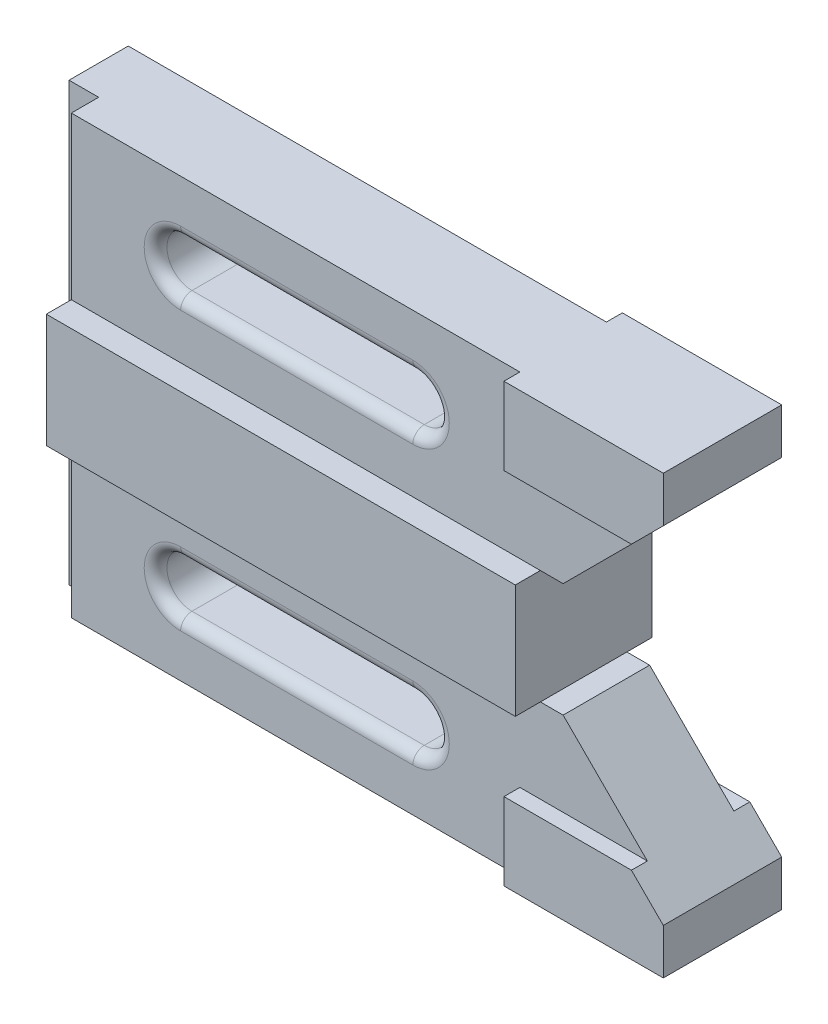
SolidWorks part; units mm, degrees
material "1060 Alloy"
ref_plane "Front Plane" through (0, 0, 0) normal (0, 0, 1) x (1, 0, 0)
ref_plane "Top Plane" through (0, 0, 0) normal (0, 1, 0) x (1, 0, 0)
ref_plane "Right Plane" through (0, 0, 0) normal (1, 0, 0) x (0, 0, -1)
sketch "Sketch2" plane through (0, 0, 0) normal (0, 0, 1) x (1, 0, 0)
  line L0 (0, 0) -> (0, 48)
  line L1 (0, 48) -> (140, 48)
  line L2 (140, 48) -> (140, 38)
  line L3 (140, 38) -> (114.5, 12.5)
  line L6 (109.5, 0) -> (0, 0)
  line L7 (-42.7721, 0) -> (218.8738, 0) construction
  line L8 (114.5, 12.5) -> (109.5, 12.5)
  line L9 (109.5, 12.5) -> (109.5, 0)
  line L10 (109.5, 12.5) -> (0, 12.5)
  line L11 (105, 48) -> (105, 31)
  line L12 (105, 31) -> (133, 31)
  line L13 (0, 30.5) -> (30.5, 30.5) construction
  line L14 (30.5, 30.5) -> (81.5, 30.5) construction
  line L15 (30.5, 36) -> (81.5, 36)
  line L16 (30.5, 25) -> (81.5, 25)
  arc A0 (30.5, 36) -> (30.5, 25) centre (30.5, 30.5) ccw
  arc A1 (81.5, 25) -> (81.5, 36) centre (81.5, 30.5) ccw
  point P16 (56, 30.5)
  dimension "D12" = 5.5
  dimension "D1" = 96
  dimension "D2" = 140
  dimension "D3" = 10
  dimension "D4" = 45
  dimension "D5" = 35.5
  dimension "D6" = 30.5
  dimension "D7" = 35
  dimension "D8" = 17
  dimension "D9" = 30.5
  dimension "D10" = 17.5
  dimension "D11" = 51
extrude "Boss-Extrude1" add sketch "Sketch2" along normal mid plane 30 contours L9 L10 L0 L6 region at (54.75, 6.25, 0)
extrude "Boss-Extrude2" add sketch "Sketch2<3>" along normal mid plane 19 contours L12 L11 L1 L0 L10 L8 L3 A1 L16 A0 L15 region at (1.3766, 30.25, 0)
sketch "Sketch2<3>" plane through (0, 0, 0) normal (0, 0, 1) x (1, 0, 0) same geometry as "Sketch2"
extrude "Boss-Extrude3" add sketch "Sketch2<4>" along normal mid plane 26 contours L11 L12 L3 L2 L1 region at (121.8487, 39.7648, 0)
sketch "Sketch2<4>" plane through (0, 0, 0) normal (0, 0, 1) x (1, 0, 0) same geometry as "Sketch2"
sketch "Sketch3" plane through (0, 48, 0) normal (0, 1, 0) x (1, 0, 0)
  line L0 (0, -3.5) -> (6.5, -3.5)
  line L1 (0, -9.5) -> (0, 9.5) construction
  line L2 (6.5, -3.5) -> (6.5, -15)
  line L3 (109.5, -15) -> (0, -15) construction
  line L4 (0, -15) -> (0, -9.5) construction
  dimension "D1" = 6.5
  dimension "D2" = 11.5
extrude "Cut-Extrude2" cut sketch "Sketch3" along normal through all and the other way through all flip side to cut
fillet "Fillet2" radius 2.5 4 edges at (25, 30.5, 9.5) (56, 25, 9.5) (87, 30.5, 9.5) (56, 36, 9.5)
mirror "Mirror3" about plane through (0, 0, 15) normal (0, -1, 0) of bodies 105
equation "\"A\"= 140"
equation "\"B\"= 51"
equation "\"C\"= 45deg"
